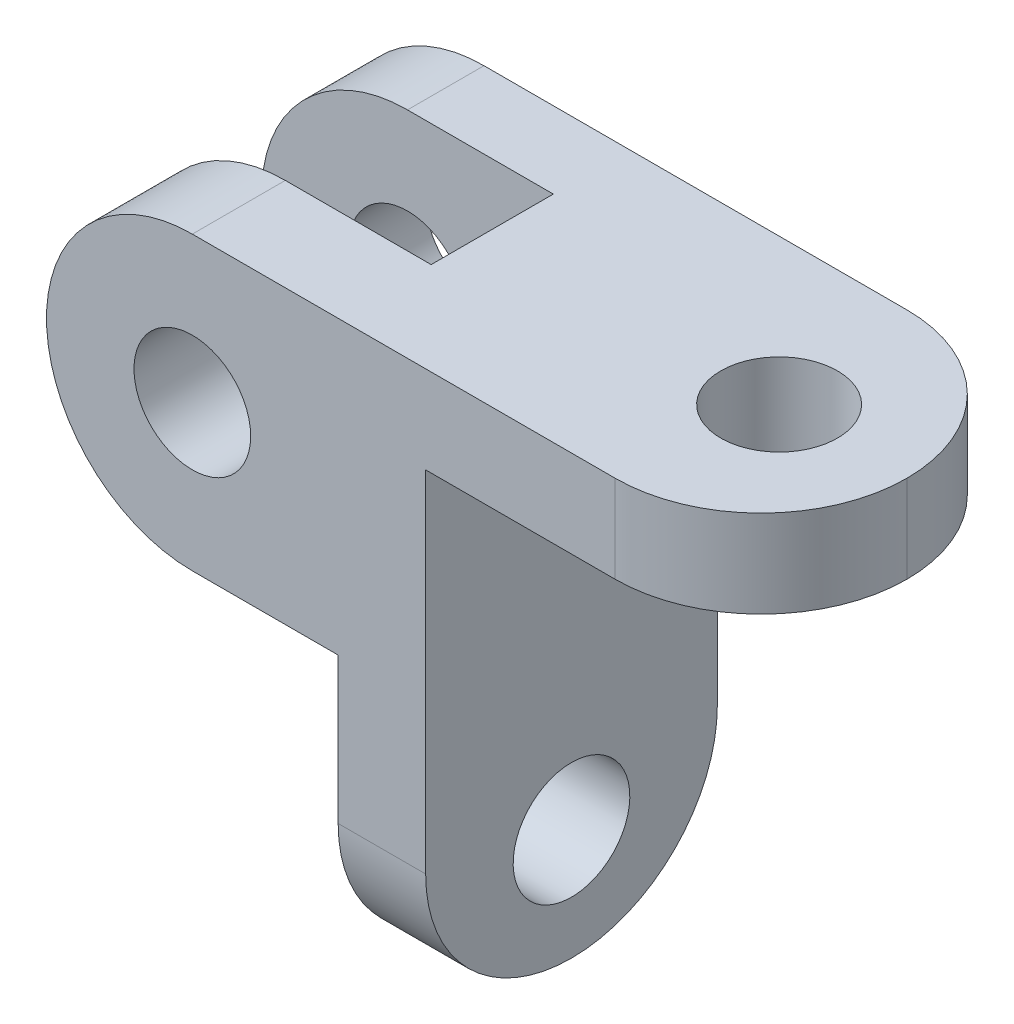
SolidWorks part; units mm, degrees
ref_plane "Front Plane" through (0, 0, 0) normal (0, 0, 1) x (1, 0, 0)
ref_plane "Top Plane" through (0, 0, 0) normal (0, 1, 0) x (1, 0, 0)
ref_plane "Right Plane" through (0, 0, 0) normal (1, 0, 0) x (0, 0, -1)
sketch "Sketch1" plane through (0, 0, 0) normal (0, 0, 1) x (1, 0, 0)
  line L0 (0, 20) -> (78, 20)
  line L1 (78, 20) -> (78, 8)
  line L2 (78, 8) -> (32, 8)
  line L3 (32, 8) -> (32, -60)
  line L4 (32, -60) -> (20, -60)
  line L5 (20, -60) -> (20, -20)
  line L6 (20, -20) -> (0, -20)
  circle A0 centre (0, 0) radius 20
  circle A1 centre (0, 0) radius 8
  dimension "D1" = 16
  dimension "D2" = 40
  dimension "D3" = 12
  dimension "D4" = 58
  dimension "D5" = 80
  dimension "D6" = 12
  dimension "D7" = 20
extrude "Boss-Extrude1" add sketch "Sketch1" along normal mid plane 40 contours A0 A1 | A0 L6 L5 L4 L3 L2 L1 L0 region at (39, 18.8827, 0) region at (13.7421, 13.7421, 0)
fillet "Fillet1" radius 20 2 edges at (78, 14, -20) (78, 14, 20)
sketch "Sketch2" plane through (0, 20, 0) normal (0, 1, 0) x (1, 0, 0)
  circle A0 centre (60.4729, 0) radius 8
  dimension "D1" = 16
extrude "Cut-Extrude2" cut sketch "Sketch2" against normal blind 16
sketch "Sketch3" plane through (0, -20, 0) normal (0, -1, 0) x (1, 0, 0)
  line L6 (20, 20) -> (20, -20) construction
  line L7 (20, -9.5067) -> (-54.4387, -9.5067)
  line L8 (20, -9.5067) -> (20, 7.2464)
  line L9 (20, 7.2464) -> (-54.4387, 7.2464)
  line L10 (-54.4387, -9.5067) -> (-54.4387, 7.2464)
extrude "Cut-Extrude3" cut sketch "Sketch3" against normal through all
fillet "Fillet2" radius 20 1 edges at (26, -60, 20)
fillet "Fillet3" radius 20 1 edges at (26, -60, -20)
sketch "Sketch4" plane through (32, 0, 0) normal (1, 0, 0) x (0, 0, -1)
  circle A0 centre (0, -44.7559) radius 8
  dimension "D1" = 16
extrude "Cut-Extrude4" cut sketch "Sketch4" against normal through all and the other way through all contours A0
